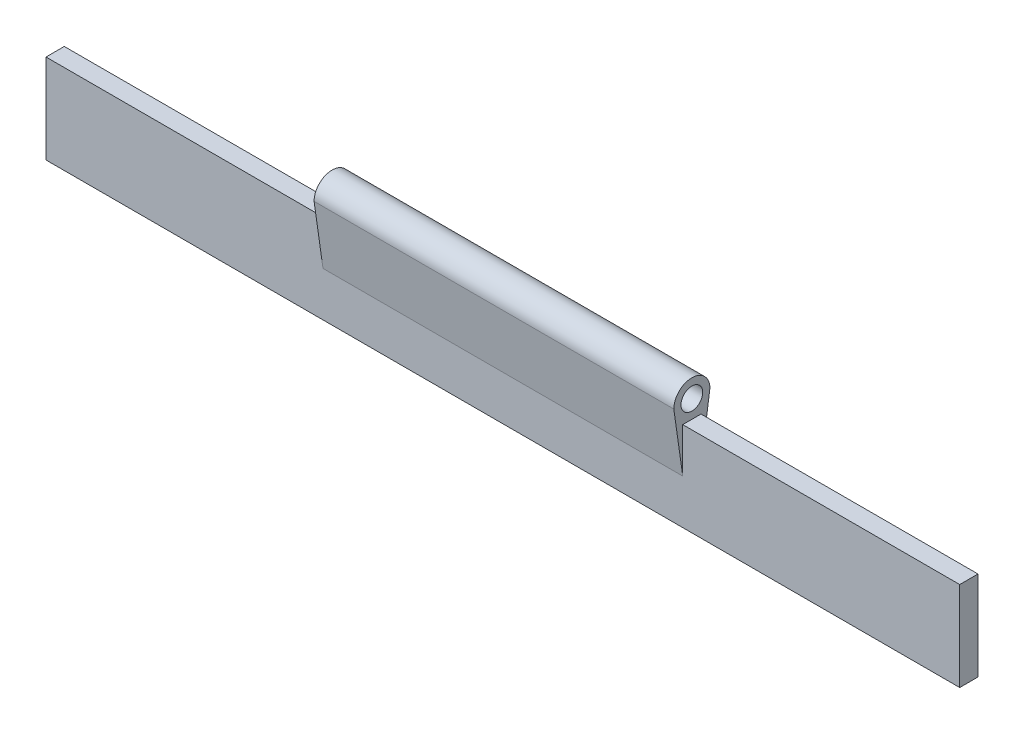
SolidWorks part; units mm, degrees
ref_plane "Front Plane" through (0, 0, 0) normal (0, 0, 1) x (1, 0, 0)
ref_plane "Top Plane" through (0, 0, 0) normal (0, 1, 0) x (1, 0, 0)
ref_plane "Right Plane" through (0, 0, 0) normal (1, 0, 0) x (0, 0, -1)
sketch "Sketch1" plane through (0, 0, 0) normal (0, 0, 1) x (1, 0, 0)
  line L0 (-63.5, 27.8) -> (-63.5, 2.4) construction
  line L1 (-63.5, 12.4) -> (63.5, 12.4)
  line L2 (-63.5, 12.4) -> (-63.5, 0)
  line L3 (-63.5, 0) -> (63.5, 0)
  line L4 (63.5, 12.4) -> (63.5, 0)
  dimension "D1" = 12.4
  dimension "D2" = 12.4
extrude "Boss-Extrude1" add sketch "Sketch1" along normal blind 2.54
sketch "Sketch2" plane through (0, 0, 0) normal (1, 0, 0) x (0, 0, -1)
  line L6 (-1.27, 12.4) -> (-1.27, 14.9) construction
  line L7 (-2.54, 12.4) -> (0, 12.4) construction
  line L8 (-2.54, 6.2) -> (-3.78, 14.9)
  line L10 (-2.54, 0) -> (-2.54, 12.4) construction
  line L11 (0, 6.2) -> (1.24, 14.9)
  line L12 (0, 0) -> (0, 12.4) construction
  line L13 (-2.54, 6.2) -> (0, 6.2)
  circle A2 centre (-1.27, 14.9) radius 1.51
  arc A3 (1.24, 14.9) -> (-3.78, 14.9) centre (-1.27, 14.9) ccw
  circle A5 centre (-1.27, 14.9) radius 2.51 construction
  point P17 (1.1303, 15.6339)
  dimension "D1" = 2.5
  dimension "D2" = 3.02
  dimension "D3" = 1
extrude "Boss-Extrude3" add sketch "Sketch2" along normal blind 25
extrude "Boss-Extrude4" add sketch "Sketch2<2>" against normal blind 25
sketch "Sketch2<2>" plane through (0, 0, 0) normal (1, 0, 0) x (0, 0, -1) same geometry as "Sketch2"
